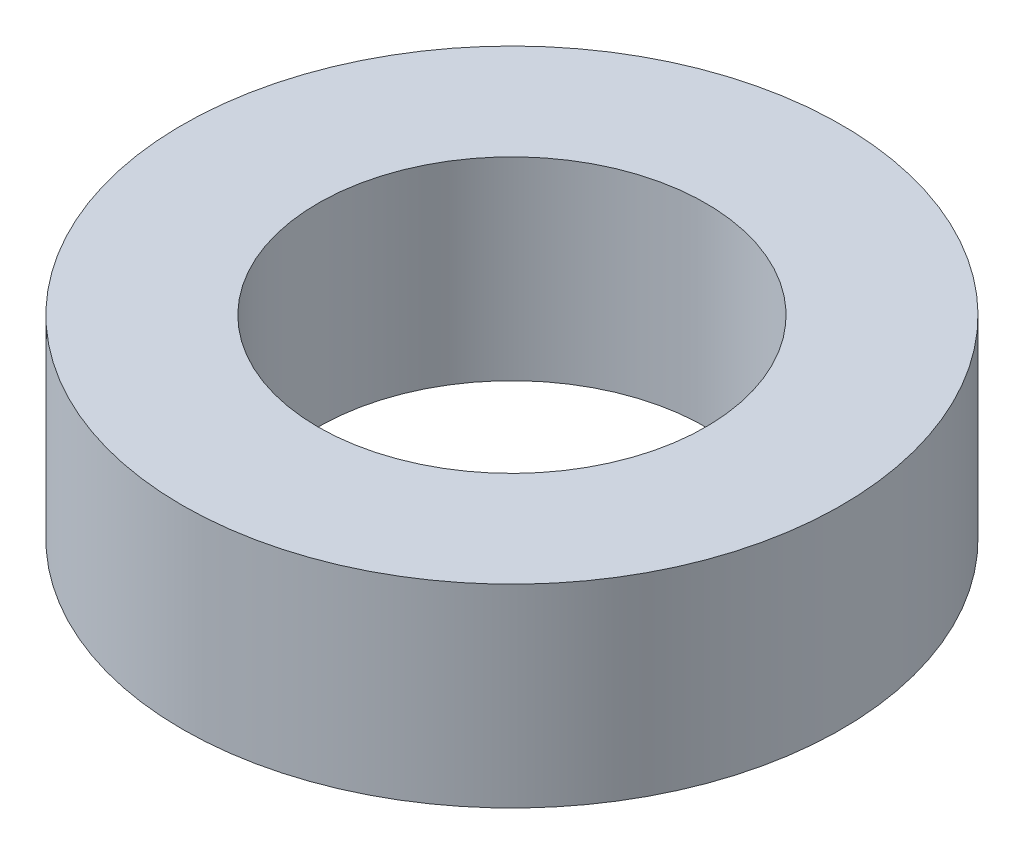
SolidWorks part; units mm, degrees
ref_plane "Front Plane" through (0, 0, 0) normal (0, 0, 1) x (1, 0, 0)
ref_plane "Top Plane" through (0, 0, 0) normal (0, 1, 0) x (1, 0, 0)
ref_plane "Right Plane" through (0, 0, 0) normal (1, 0, 0) x (0, 0, -1)
sketch "Sketch1" plane through (0, 0, 0) normal (0, 1, 0) x (1, 0, 0)
  circle A0 centre (0, 0) radius 42.5
  dimension "FLANGE_OD" = 85
extrude "Boss-Extrude1" add sketch "Sketch1" along normal blind 25
sketch "Sketch2" plane through (0, 0, 0) normal (0, 1, 0) x (1, 0, 0)
  circle A0 centre (0, 0) radius 25
  dimension "BORE_D" = 50
extrude "Cut-Extrude1" cut sketch "Sketch2" along normal through all
sketch "Sketch3" plane through (0, 25, 0) normal (0, 1, 0) x (1, 0, 0)
  circle A0 centre (0, 0) radius 15.4843 construction
  circle A1 centre (-15.4843, 0) radius 1.7596
  dimension "BOLT_D" = 3.5192
  dimension "BOLT_PCD" = 30.9686
extrude "Cut-Extrude2" cut sketch "Sketch3" against normal blind 23.0851 rebuild error yes
pattern_circular "CirPattern1" count 3 over 360 rebuild error yes
